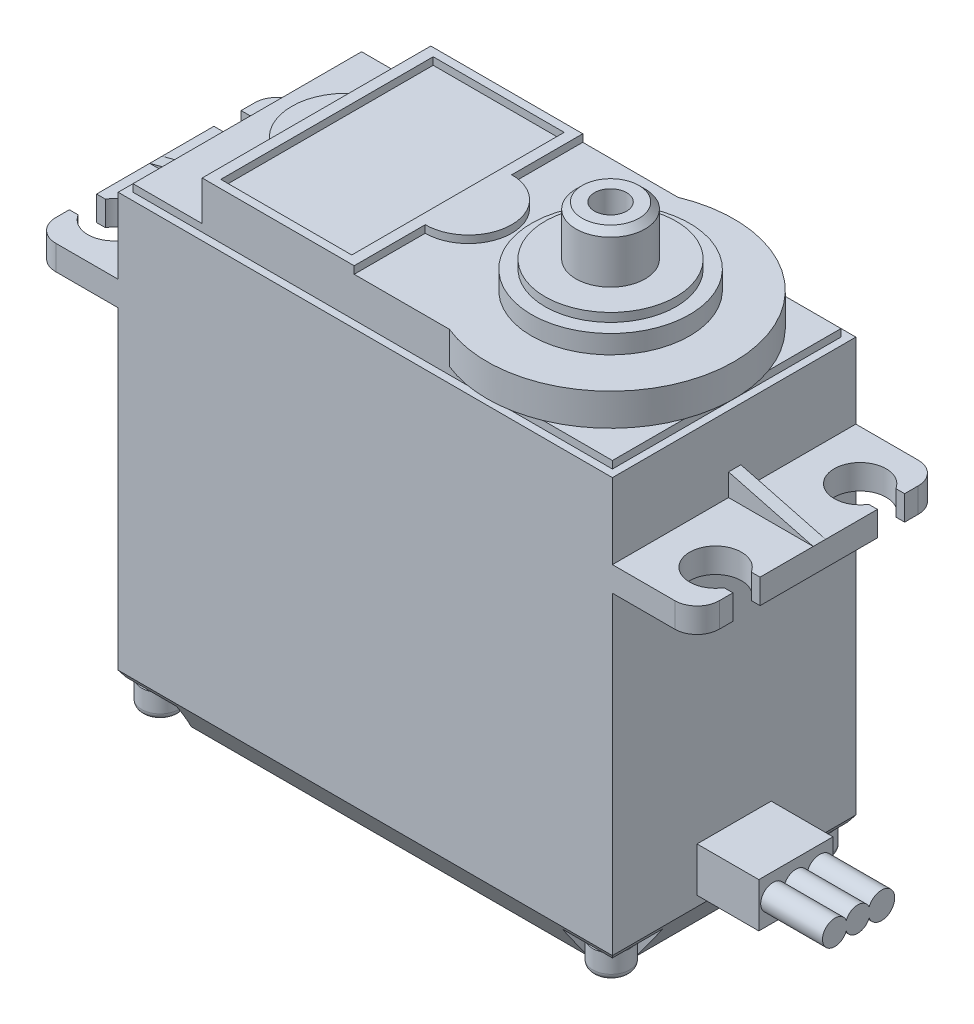
SolidWorks part; units mm, degrees
ref_plane "Front Plane" through (0, 0, 0) normal (0, 0, 1) x (1, 0, 0)
ref_plane "Top Plane" through (0, 0, 0) normal (0, 1, 0) x (1, 0, 0)
ref_plane "Right Plane" through (0, 0, 0) normal (1, 0, 0) x (0, 0, -1)
sketch "Sketch1" plane through (0, 0, 0) normal (0, 0, 1) x (1, 0, 0)
  line L1 (20, -18.25) -> (-20, -18.25)
  line L2 (20, -18.25) -> (20, 18.25)
  line L3 (20, 18.25) -> (-20, 18.25)
  line L4 (-20, -18.25) -> (-20, 18.25)
  line L5 (20, -18.25) -> (-20, 18.25) construction
  line L6 (20, 18.25) -> (-20, -18.25) construction
  point P0 (0, 0)
  dimension "D1" = 40
  dimension "D2" = 36.5
extrude "Boss-Extrude1" add sketch "Sketch1" along normal blind 19.7 contours L4 L3 L2 L1
chamfer "Chamfer1" distance 2 distance2 3 4 edges at (0, -18.25, 0) (-20, -18.25, 9.85) (0, -18.25, 19.7) (20, -18.25, 9.85) first distance on face at (0, -18.25, 9.85)
sketch "Sketch2" plane through (0, -18.25, 0) normal (0, -1, 0) x (1, 0, 0)
  line L0 (20, 19.7) -> (20, 0) construction
  line L1 (-20, 19.7) -> (20, 19.7) construction
  line L2 (20, 0) -> (-20, 0) construction
  line L3 (-20, 0) -> (-20, 19.7) construction
  line L6 (20, 15.3) -> (20, 19.7)
  line L7 (20, 19.7) -> (15.6, 19.7)
  line L10 (20, 4.4) -> (20, 0)
  line L11 (20, 0) -> (15.6, 0)
  line L13 (-15.6, 0) -> (-20, 0)
  line L16 (-20, 0) -> (-20, 4.4)
  line L18 (-20, 15.3) -> (-20, 19.7)
  line L19 (-20, 19.7) -> (-15.6, 19.7)
  arc A0 (20, 15.3) -> (15.6, 19.7) centre (20, 19.7) cw
  arc A1 (20, 4.4) -> (15.6, 0) centre (20, 0) ccw
  arc A2 (-20, 4.4) -> (-15.6, 0) centre (-20, 0) cw
  arc A3 (-15.6, 19.7) -> (-20, 15.3) centre (-20, 19.7) cw
  dimension "D1" = 4.4
extrude "Cut-Extrude1" cut sketch "Sketch2" against normal blind 2.5
sketch "Sketch4" plane through (0, -15.75, 0) normal (0, -1, 0) x (1, 0, 0)
  circle A0 centre (-18.295, 18.0012) radius 1.5
  circle A1 centre (18.205, 18.0012) radius 1.5
  circle A2 centre (18.205, 1.7512) radius 1.5
  circle A3 centre (-18.295, 1.7512) radius 1.5
  dimension "D1" = 3
  dimension "D2" = 2
  dimension "D3" = 2
extrude "Boss-Extrude2" add sketch "Sketch4" along normal blind 2 contours A1 | A2 | A3 | A0 region at (18.205, -15.75, 18.0012) region at (18.205, -15.75, 1.7512) region at (-18.295, -15.75, 1.7512)
fillet "Fillet1" radius 0.5 1 edges at (-16.795, -17.75, 18.0012)
fillet "Fillet3" radius 0.5 1 edges at (-16.795, -17.75, 1.7512)
fillet "Fillet4" radius 0.5 1 edges at (19.705, -17.75, 1.7512)
fillet "Fillet5" radius 0.5 1 edges at (19.705, -17.75, 18.0012)
ref_plane "Plane1" through (0, 10.15, 0) normal (0, -1, 0) x (-1, 0, 0)
sketch "Sketch5" plane through (0, 10.15, 0) normal (0, -1, 0) x (-1, 0, 0)
  line L0 (20, -19.7) -> (-20, 0)
  line L1 (20, -19.7) -> (-20, -19.7)
  line L2 (20, -19.7) -> (20, 0)
  line L3 (20, 0) -> (-20, 0)
  line L4 (-20, -19.7) -> (-20, 0)
  line L5 (-20, -19.7) -> (20, 0)
  line L7 (26.85, 0) -> (-26.85, 0)
  line L8 (26.85, 0) -> (26.85, -19.7)
  line L9 (26.85, -19.7) -> (-26.85, -19.7)
  line L10 (-26.85, 0) -> (-26.85, -19.7)
  line L11 (26.85, 0) -> (-26.85, -19.7) construction
  line L12 (26.85, -19.7) -> (-26.85, 0) construction
  point P6 (0, -9.85)
  dimension "D1" = 53.7
extrude "Boss-Extrude3" add sketch "Sketch5" against normal blind 2 contours L10 L9 L8 L7
sketch "Sketch6" plane through (0, 10.15, 0) normal (0, -1, 0) x (1, 0, 0)
  line L0 (-20, 19.7) -> (-26.85, 19.7) construction
  line L1 (26.85, 14.6) -> (26.1389, 14.6)
  line L2 (26.85, 0) -> (26.85, 19.7) construction
  line L3 (26.85, 14.6) -> (26.85, 16.8)
  line L4 (26.85, 2.9) -> (26.1389, 2.9)
  line L5 (0, 19.7) -> (0, 0) construction
  line L6 (26.85, 16.8) -> (26.1389, 16.8)
  line L7 (-20, 19.7) -> (20, 19.7) construction
  line L8 (26.85, 9.85) -> (-26.85, 9.85) construction
  line L9 (-26.85, 0) -> (-26.85, 19.7) construction
  line L10 (26.85, 5.1) -> (26.85, 2.9)
  line L11 (26.85, 5.1) -> (26.1389, 5.1)
  line L12 (26.85, 0) -> (26.85, 19.7) construction
  line L14 (26.85, 0) -> (26.85, 19.7) construction
  line L15 (-26.85, 5.1) -> (-26.1389, 5.1)
  line L16 (-26.85, 5.1) -> (-26.85, 2.9)
  line L17 (-26.85, 16.8) -> (-26.1389, 16.8)
  line L18 (-26.85, 2.9) -> (-26.1389, 2.9)
  line L19 (-26.85, 14.6) -> (-26.85, 16.8)
  line L20 (-26.85, 14.6) -> (-26.1389, 14.6)
  arc A0 (26.1389, 16.8) -> (26.1389, 14.6) centre (24.35, 15.7) ccw
  arc A1 (26.1389, 2.9) -> (26.1389, 5.1) centre (24.35, 4) cw
  arc A2 (-26.1389, 2.9) -> (-26.1389, 5.1) centre (-24.35, 4) ccw
  arc A3 (-26.1389, 16.8) -> (-26.1389, 14.6) centre (-24.35, 15.7) cw
  point P15 (26.85, 15.7)
  point P28 (26.85, 4)
  point P39 (-26.85, 4)
  point P40 (-26.85, 15.7)
  dimension "D1" = 4.2
  dimension "D2" = 4
  dimension "D3" = 2.2
  dimension "D4" = 2.5
  dimension "D5" = 2.5
  dimension "D6" = 0.7111
extrude "Cut-Extrude2" cut sketch "Sketch6" against normal blind 2
fillet "Fillet9" radius 1.8 4 edges at (26.85, 11.15, 0) (-26.85, 11.15, 0) (-26.85, 11.15, 19.7) (26.85, 11.15, 19.7)
ref_plane "Plane2" through (0, 0, 10.3) normal (0, 0, 1) x (1, 0, 0)
sketch "Sketch7" plane through (0, 0, 10.3) normal (0, 0, 1) x (1, 0, 0)
  line L0 (-26.85, 12.15) -> (-20, 13.95)
  line L2 (-26.85, 12.15) -> (-20, 12.15)
  line L3 (-20, 12.15) -> (-20, 13.95)
  line L4 (0, -1000) -> (0, 49000) construction
  line L5 (20, 12.15) -> (20, 13.95)
  line L6 (26.85, 12.15) -> (20, 12.15)
  line L7 (26.85, 12.15) -> (20, 13.95)
  dimension "D1" = 1.8
extrude "Boss-Extrude4" add sketch "Sketch7" against normal blind 1
sketch "Sketch8" plane through (0, 18.25, 0) normal (0, 1, 0) x (1, 0, 0)
  line L0 (20, -19.7) -> (-20, 0) construction
  line L1 (20, 0) -> (-20, -19.7) construction
  line L2 (20, -19.7) -> (-20, -19.7) construction
  line L3 (-19.4, -0.6) -> (19.4, -0.6)
  line L4 (-19.4, -0.6) -> (-19.4, -19.1)
  line L5 (-19.4, -19.1) -> (19.4, -19.1)
  line L6 (19.4, -0.6) -> (19.4, -19.1)
  line L7 (-19.4, -0.6) -> (19.4, -19.1) construction
  line L8 (-19.4, -19.1) -> (19.4, -0.6) construction
  line L9 (20, -10.3) -> (20, -19.7) construction
  point P8 (0, -9.85)
  point P9 (0, -9.85)
  dimension "D1" = 0.6
  dimension "D2" = 0.6
extrude "Boss-Extrude5" add sketch "Sketch8" along normal blind 0.6 contours L6 L5 L4 L3
sketch "Sketch9" plane through (0, 18.85, 0) normal (0, 1, 0) x (1, 0, 0)
  line L0 (20, -19.7) -> (20, 0) construction
  line L1 (-13.7997, -6.1622) -> (-13.7997, -0.6)
  line L2 (6.2003, -19.1) -> (-13.7997, -19.1)
  line L3 (6.2003, -0.6) -> (-13.7997, -0.6)
  line L4 (-13.7997, -19.1) -> (-13.7997, -13.5378)
  line L5 (-19.4, -19.1) -> (19.4, -19.1) construction
  arc A0 (6.2003, -19.1) -> (6.2003, -0.6) centre (10, -9.85) ccw
  arc A1 (-13.7997, -6.1622) -> (-13.7997, -13.5378) centre (-11.3997, -9.85) ccw
  point P2 (20, -9.85)
  dimension "D1" = 10
  dimension "D2" = 20
  dimension "D4" = 8.8
  dimension "D3" = 20
  dimension "D5" = 2.4
extrude "Boss-Extrude6" add sketch "Sketch9" along normal blind 2.6
sketch "Sketch10" plane through (0, 21.45, 0) normal (0, 1, 0) x (1, 0, 0)
  line L0 (-13.7997, -19.1) -> (-13.7997, -0.6)
  line L1 (-13.7997, -19.1) -> (-1.4997, -19.1)
  line L2 (-13.7997, -0.6) -> (-1.4997, -0.6)
  line L3 (-1.4997, -19.1) -> (-1.4997, -13.35)
  line L4 (-13.7997, -9.85) -> (-1.4997, -9.85) construction
  line L5 (-12.9497, -1.2547) -> (-2.3497, -1.2547)
  line L6 (-12.9497, -1.2547) -> (-12.9497, -18.4453)
  line L7 (-12.9497, -18.4453) -> (-2.3497, -18.4453)
  line L8 (-2.3497, -1.2547) -> (-2.3497, -18.4453)
  line L9 (-12.9497, -1.2547) -> (-2.3497, -18.4453) construction
  line L10 (-12.9497, -18.4453) -> (-2.3497, -1.2547) construction
  line L11 (-7.6497, -19.1) -> (-7.6497, -0.6) construction
  line L12 (-1.4997, -6.35) -> (-1.4997, -0.6)
  arc A0 (-1.4997, -13.35) -> (-1.4997, -6.35) centre (-1.4997, -9.85) ccw
  point P0 (-7.6497, -9.85)
  dimension "D3" = 3.5
  dimension "D1" = 12.3
  dimension "D2" = 10.6
extrude "Boss-Extrude7" add sketch "Sketch10" along normal blind 0.6
sketch "Sketch11" plane through (0, 21.45, 0) normal (0, 1, 0) x (1, 0, 0)
  circle A0 centre (10, -9.85) radius 6.4
  dimension "D1" = 12.8
extrude "Boss-Extrude8" add sketch "Sketch11" along normal blind 1.5
sketch "Sketch12" plane through (0, 22.95, 0) normal (0, 1, 0) x (1, 0, 0)
  circle A0 centre (10, -9.85) radius 5.3
extrude "Boss-Extrude9" add sketch "Sketch12" along normal blind 0.7
sketch "Sketch13" plane through (0, 23.65, 0) normal (0, 1, 0) x (1, 0, 0)
  circle A0 centre (10, -9.85) radius 2.8
  circle A1 centre (10, -9.85) radius 1.3
  dimension "D1" = 5.6
extrude "Boss-Extrude10" add sketch "Sketch13" along normal blind 4 contours A0 A1 region at (7.2792, 23.65, 9.85)
chamfer "Chamfer2" distance 0.5 angle 45 1 edges at (10, 27.65, 12.65)
sketch "Sketch14" plane through (0, 23.65, 0) normal (0, 1, 0) x (1, 0, 0)
  line L0 (10, -9.85) -> (10, -12.15)
  line L1 (10, -9.85) -> (9.428, -12.0777)
  line L2 (10, -9.85) -> (8.892, -11.8655)
  line L3 (10, -9.85) -> (8.4255, -11.5266)
  line L4 (10, -9.85) -> (8.058, -11.0824)
  line L5 (10, -9.85) -> (7.8126, -10.5607)
  line L6 (10, -9.85) -> (7.7045, -9.9944)
  line L7 (10, -9.85) -> (7.7407, -9.419)
  line L8 (10, -9.85) -> (7.9189, -8.8707)
  line L9 (10, -9.85) -> (8.2278, -8.3839)
  line L10 (10, -9.85) -> (8.6481, -7.9893)
  line L11 (10, -9.85) -> (9.1533, -7.7115)
  line L12 (10, -9.85) -> (9.7117, -7.5681)
  line L13 (10, -9.85) -> (10.2883, -7.5681)
  line L14 (10, -9.85) -> (10.8467, -7.7115)
  line L15 (10, -9.85) -> (11.3519, -7.9893)
  line L16 (10, -9.85) -> (11.7722, -8.3839)
  line L17 (10, -9.85) -> (12.0811, -8.8707)
  line L18 (10, -9.85) -> (12.2593, -9.419)
  line L19 (10, -9.85) -> (12.2955, -9.9944)
  line L20 (10, -9.85) -> (12.1874, -10.5607)
  line L21 (10, -9.85) -> (11.942, -11.0824)
  line L22 (10, -9.85) -> (11.5745, -11.5266)
  line L23 (10, -9.85) -> (11.108, -11.8655)
  line L24 (10, -9.85) -> (10.572, -12.0777)
  circle A0 centre (10, -9.85) radius 2.8
  circle A1 centre (10, -9.85) radius 2.3
  point P32 (10, -9.85)
  dimension "D1" = 25
sketch "Sketch15" plane through (0, -17.75, 0) normal (0, -1, 0) x (1, 0, 0)
  line L0 (18.055, 1.6012) -> (18.055, 0.9012)
  line L1 (18.355, 2.6012) -> (18.055, 2.6012)
  line L2 (18.355, 2.6012) -> (18.355, 1.9012)
  line L3 (18.355, 0.9012) -> (18.055, 0.9012)
  line L4 (18.055, 2.6012) -> (18.055, 1.9012)
  line L5 (18.355, 2.6012) -> (18.055, 0.9012) construction
  line L6 (18.355, 0.9012) -> (18.055, 2.6012) construction
  line L7 (17.355, 1.6012) -> (18.055, 1.6012)
  line L8 (17.355, 1.6012) -> (17.355, 1.9012)
  line L9 (17.355, 1.9012) -> (18.055, 1.9012)
  line L10 (19.055, 1.6012) -> (19.055, 1.9012)
  line L11 (17.355, 1.6012) -> (19.055, 1.9012) construction
  line L12 (17.355, 1.9012) -> (19.055, 1.6012) construction
  line L13 (18.355, 1.6012) -> (19.055, 1.6012)
  line L14 (18.355, 1.9012) -> (19.055, 1.9012)
  line L15 (18.355, 1.6012) -> (18.355, 0.9012)
  point P0 (18.205, 1.7512)
  point P6 (18.205, 1.7512)
  dimension "D1" = 0.3
  dimension "D2" = 0.3
  dimension "D3" = 1.7
  dimension "D4" = 1.7
extrude "Cut-Extrude3" cut sketch "Sketch15" against normal blind 1.2
pattern_linear "LPattern1" count 2 spacing 36.5 along (-1, 0, 0) count 2 spacing 16.3 along (0, 0, 1) of "Cut-Extrude3"
sketch "Sketch16" plane through (20, 0, 0) normal (1, 0, 0) x (0, 0, -1)
  line L1 (-6.85, -10.85) -> (-12.85, -10.85)
  line L2 (-6.85, -10.85) -> (-6.85, -14.45)
  line L3 (-6.85, -14.45) -> (-12.85, -14.45)
  line L4 (-12.85, -10.85) -> (-12.85, -14.45)
  line L5 (-6.85, -10.85) -> (-12.85, -14.45) construction
  line L6 (-6.85, -14.45) -> (-12.85, -10.85) construction
  line L11 (-9.85, 18.25) -> (-9.85, -18.25) construction
  line L12 (-0.6, 18.25) -> (-19.1, 18.25) construction
  line L13 (-3.9192, -18.25) -> (-15.7808, -18.25) construction
  point P0 (-9.85, -12.65)
  dimension "D1" = 3.6
  dimension "D2" = 6
  dimension "D3" = 3.8
extrude "Boss-Extrude11" add sketch "Sketch16" along normal blind 5
sketch "Sketch17" plane through (25, 0, 0) normal (1, 0, 0) x (0, 0, -1)
  line L0 (-6.85, -14.45) -> (-6.85, -10.85) construction
  arc A0 (-10.775, -13.0016) -> (-8.925, -13.0016) centre (-9.85, -12.6216) ccw
  arc A1 (-8.925, -13.0016) -> (-8.925, -12.2417) centre (-7.9223, -12.6216) ccw
  arc A2 (-10.775, -12.2417) -> (-10.775, -13.0016) centre (-11.7, -12.6216) ccw
  arc A3 (-8.925, -12.2417) -> (-10.775, -12.2417) centre (-9.85, -12.6216) ccw
  dimension "D1" = 2
  dimension "D2" = 3
extrude "Boss-Extrude16" add sketch "Sketch17" along normal blind 5 contours A2 A0 A1 A3
extrude "Boss-Extrude42" add sketch "Sketch17<9>" along normal blind 5 contours A2 A0 A1 A3
sketch "Sketch17<9>" plane through (25, 0, 0) normal (1, 0, 0) x (0, 0, -1) same geometry as "Sketch17"
